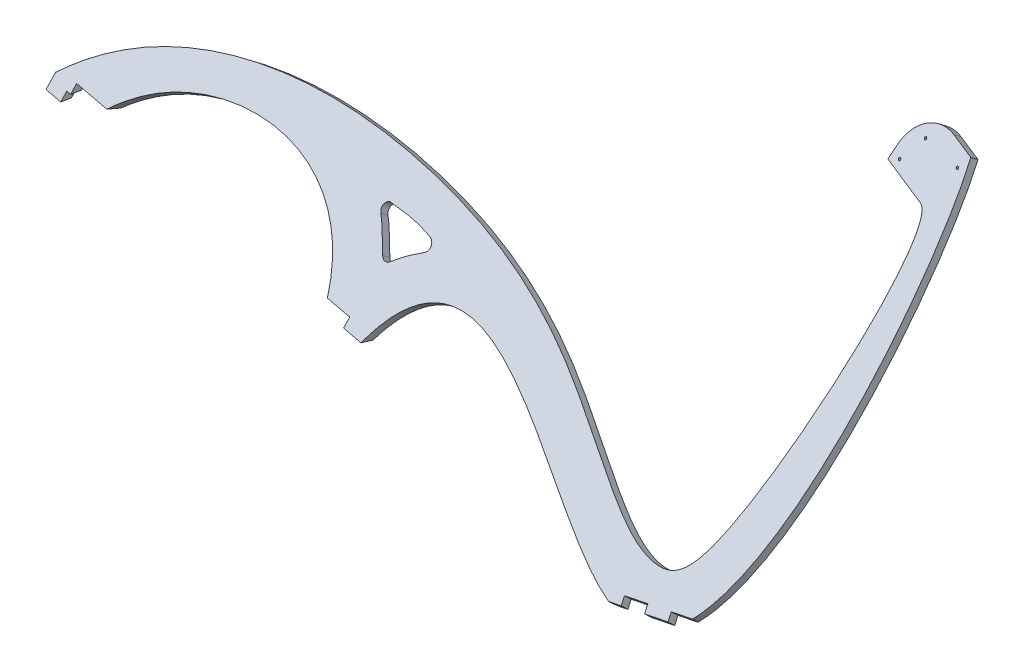
SolidWorks part; units mm, degrees
ref_plane "Front Plane" through (0, 0, 0) normal (0, 0, 1) x (1, 0, 0)
ref_plane "Top Plane" through (0, 0, 0) normal (0, 1, 0) x (1, 0, 0)
ref_plane "Right Plane" through (0, 0, 0) normal (1, 0, 0) x (0, 0, -1)
ref_plane "Plane1" through (247.5119, 247.5119, -680.0333) normal (-0.3236, -0.3236, 0.8891) x (0.9462, -0.1107, 0.3041)
ref_axis "Axis1" through (1039.3698, 513.9591, -294.8417) along (-0.9454, 0.1498, -0.2896)
sketch "Sketch1" plane through (17.4996, -61.6138, -87.0647) normal (0.1568, -0.5697, -0.8068) x (-0.9876, -0.0871, -0.1305)
  line L0 (-848.888, 45.7598) -> (366.2309, 175.3119) construction
  line L1 (334.7635, 186.6404) -> (364.595, 189.8209) construction
  line L2 (-225.3142, 126.9267) -> (-260.7406, 123.1496)
  line L3 (334.7635, 186.6404) -> (336.3995, 172.1314) construction
  line L4 (365.1946, 183.566) -> (363.5586, 198.075) construction
  line L5 (366.1265, 175.3008) -> (363.5586, 198.075)
  line L6 (-1005.1456, 627.3782) -> (-1005.4224, 627.1712) construction
  line L7 (366.1265, 175.3008) -> (336.3995, 172.1314)
  line L8 (336.3995, 172.1314) -> (334.7635, 186.6404)
  line L9 (-1058.1671, 586.5088) -> (-906.3804, 631.7276) construction
  line L10 (-1032.2646, 594.2254) -> (-731.2, 683.9156) construction
  line L11 (-1026.3239, 684.8448) -> (-924.6621, 715.1309)
  line L12 (-924.6621, 715.1309) -> (-906.3804, 631.7276)
  line L13 (-927.8383, 59.6968) -> (-770.1655, 32.5073) construction
  line L14 (-711.049, 22.3131) -> (-907.4588, 56.1825) construction
  line L15 (334.7635, 186.6404) -> (326.9877, 185.8113)
  line L16 (-927.8383, 59.6968) -> (-923.59, 84.3331) construction
  line L17 (-923.59, 84.3331) -> (-765.9171, 57.1436) construction
  line L18 (-227.329, 141.3953) -> (-225.3142, 126.9267)
  line L19 (-765.9171, 57.1436) -> (-770.1655, 32.5073) construction
  line L20 (-849.0019, 46.102) -> (-841.4008, 90.1812) construction
  line L21 (-982.2737, 609.1182) -> (-906.3804, 631.7276)
  line L22 (-260.7406, 123.1496) -> (-225.3142, 126.9267) construction
  line L23 (-227.329, 141.3953) -> (-225.3142, 126.9267) construction
  line L24 (325.4398, 200.3297) -> (264.5058, 193.8331)
  line L25 (-227.329, 141.3953) -> (-182.2193, 146.2047)
  line L26 (-849.0019, 46.102) -> (-854.1752, 16.102) construction
  line L27 (-182.2193, 146.2047) -> (-227.329, 141.3953)
  line L28 (-227.329, 141.3953) -> (-257.1753, 138.2132)
  line L29 (-227.329, 141.3953) -> (-257.1753, 138.2132) construction
  line L30 (-182.2193, 146.2047) -> (-227.329, 141.3953) construction
  line L31 (325.4398, 200.3297) -> (264.5058, 193.8331) construction
  line L32 (325.4398, 200.3297) -> (326.9877, 185.8113)
  line L33 (325.4398, 200.3297) -> (326.9877, 185.8113)
  line L34 (325.4398, 200.3297) -> (264.5058, 193.8331)
  ellipse E0 centre (76.7309, -163.7713) end of major axis (10.5208, 457.2386) minor radius 355.7705 (-257.1753, 138.2132) -> (-260.7406, 123.1496) ccw construction
  spline S0 degree 3 poles (-982.2737, 609.1182) (-1029.6096, 598.293) (-938.6177, 119.1677) (-844.1848, 81.5427) (-750.4586, 111.4734) (-542.5515, 265.8857) (-159.6817, 379.449) (217.4268, 343.7924) (363.5586, 198.075) knots 0 0 0 0 0.220807 0.303233 0.390142 0.497709 0.653994 1 1 1 1
  spline S1 degree 3 poles (-182.2193, 146.2047) (-137.5596, 288.6615) (94.0163, 311.7011) (234.6001, 223.2366) (264.5058, 193.8331) knots 0 0 0 0 0.72161 0.964477 0.964477 0.964477 0.964477
  spline S2 degree 3 poles (-1026.3239, 684.8448) (-1056.5086, 520.532) (-1000.6634, -421.934) (-393.994, 393.2132) (-260.7406, 123.1496) knots 0 0 0 0 0.513113 1 1 1 1
  dimension "D2" = 80
  dimension "D3" = 80
  dimension "D4" = 25
  dimension "D5" = 30
ref_plane "Plane2" through (32.3075, 32.3075, -88.7641) normal (-0.3236, -0.3236, 0.8891) x (0.9462, -0.1107, 0.3041)
ref_plane "Plane3" through (734.8882, 76.1719, 295.2017) normal (-0.9237, -0.0957, -0.371) x (-0.3691, -0.0383, 0.9286)
ref_axis "Axis2" through (710.5526, 368.3269, 280.3979) along (0.2052, -0.9413, -0.2679)
sketch "Sketch2" plane through (11.2801, -57.0409, 57.2996) normal (0.1382, -0.6987, 0.7019) x (0.9904, 0.0904, -0.105)
  line L12 (847.9784, 66.4873) -> (852.7457, 41.946) construction
  line L18 (774.2138, 26.6907) -> (931.2777, 57.2013) construction
  line L19 (931.2777, 57.2013) -> (926.5104, 81.7426) construction
  line L20 (926.5104, 81.7426) -> (769.4465, 51.2319) construction
  line L21 (769.4465, 51.2319) -> (774.2138, 26.6907) construction
  line L22 (852.7457, 41.946) -> (858.4665, 12.4965) construction
  dimension "D1" = 25
  dimension "D2" = 30
ref_plane "Plane4" through (744.3294, 384.7233, 304.283) normal (-0.3236, 0.8891, 0.3236) x (0.9397, 0.342, 0)
sketch "Sketch4" plane through (744.3294, 384.7233, 304.283) normal (-0.3236, 0.8891, 0.3236) x (0.9397, 0.342, 0)
  line L0 (75.8923, -10) -> (123.4751, -10)
  line L1 (123.4751, -10) -> (123.4751, 153.8205)
  line L2 (75.8923, 48.8458) -> (75.8923, 153.8205) construction
  line L3 (75.8923, 153.8205) -> (-79.8307, 153.8205)
  line L4 (-79.8307, -10) -> (-79.8307, 153.8205)
  line L5 (123.4751, 153.8205) -> (75.8923, 153.8205)
  line L6 (75.8923, 48.8458) -> (75.8923, -10) construction
  line L7 (75.8923, -10) -> (-79.8307, -10)
  line L8 (80, -10) -> (-43.6414, -10) construction
  dimension "D1" = 155.723
  dimension "D2" = 163.8205
  dimension "D3" = 58.8458
  dimension "D4" = 47.5828
extrude "Boss-Extrude2" add sketch "Sketch1" along normal blind 12 separate body contours L11 S2 L2 S1 S0 L21 L12 region at (486.3942, 197.6823, -179.0082)
fillet "Fillet1" radius 60 1 edges at (934.526, 599.9752, -383.3936)
fillet "Fillet2" radius 30 1 edges at (990.9986, 518.3564, -314.786)
sketch "Sketch13" plane through (18.832, -68.408, -96.8824) normal (0.1568, -0.5697, -0.8068) x (-0.9876, -0.0906, -0.128)
  arc A0 (-235.8752, 221.376) -> (-250.639, 219.3586) centre (-244.1602, 226.976) cw
  arc A1 (-295.3968, 250.3387) -> (-293.0699, 268.7568) centre (-290.5424, 259.0814) cw
  arc A2 (-213.0974, 278.6163) -> (-205.5275, 261.6168) centre (-212.6601, 268.6259) cw
  spline S0 degree 3 poles (-293.0699, 268.7568) (-292.4947, 268.907) (-261.9123, 276.8067) (-239.7929, 277.4476) (-213.0974, 278.6163) knots 0.445827 0.445827 0.445827 0.445827 0.44834 0.580052 0.580052 0.580052 0.580052
  spline S3 degree 3 poles (-295.3968, 250.3387) (-282.0863, 242.9481) (-266.8858, 232.7869) (-252.8897, 221.2729) (-250.639, 219.3586) knots 0.719716 0.719716 0.719716 0.719716 0.79687 0.811921 0.811921 0.811921 0.811921
  spline S5 degree 3 poles (-235.8752, 221.376) (-232.7991, 225.9271) (-220.1586, 243.2214) (-212.8497, 254.1656) (-205.5275, 261.6168) knots 0.147762 0.147762 0.147762 0.147762 0.170979 0.239181 0.239181 0.239181 0.239181
  dimension "D1" = 10
sketch "Sketch14" plane through (10.9247, -56.0037, 56.203) normal (0.1364, -0.6993, 0.7017) x (0.9907, 0.096, -0.0969)
  line L0 (816.7452, 27.0278) -> (821.0315, 3.7163)
  line L1 (821.0315, 3.7163) -> (860.3924, 10.8394)
  line L2 (860.3924, 10.8394) -> (856.0857, 34.2614)
  line L3 (895.4262, 41.495) -> (899.7532, 17.9626)
  line L4 (899.7532, 17.9626) -> (940.8385, 25.3978)
  line L5 (940.8385, 25.3978) -> (940.8385, 74.0524)
  line L7 (895.4262, 41.495) -> (856.0857, 34.2614)
  line L10 (816.7452, 27.0278) -> (792.6014, 22.5885)
  line L23 (827.9034, 545.3306) -> (696.2019, 529.5358)
  line L24 (688.0254, 516.1063) -> (698.6127, 487.7765)
  line L29 (698.6127, 487.7765) -> (780.079, 496.7776)
  line L30 (-323.9964, 221.96) -> (-316.4535, 220.9381)
  line L31 (-323.9964, 221.96) -> (-316.4535, 220.9381)
  line L36 (-316.4535, 220.9381) -> (-314.2, 237.5723)
  line L38 (268.023, 141.7575) -> (270.8794, 153.8295)
  line L39 (796.2366, 21.4509) -> (817.0727, 25.2821)
  line L40 (817.0727, 25.2821) -> (818.8085, 15.8459)
  line L41 (820.9388, 15.46) -> (858.2628, 22.4606)
  line L42 (858.2628, 22.4606) -> (856.4132, 32.5157)
  line L43 (856.4132, 32.5157) -> (895.7537, 39.7493)
  line L44 (895.7537, 39.7493) -> (897.5775, 29.8346)
  line L45 (897.5775, 29.8346) -> (908.6107, 31.904)
  line L46 (827.9034, 545.3306) -> (696.2019, 529.5358)
  line L47 (688.0254, 516.1063) -> (698.6127, 487.7765)
  line L52 (698.6127, 487.7765) -> (780.079, 496.7776)
  line L59 (-316.4535, 220.9381) -> (-314.2, 237.5723)
  line L61 (268.023, 141.7575) -> (270.8794, 153.8295)
  line L68 (895.4262, 41.495) -> (856.0857, 34.2614) construction
  line L111 (774.7231, 19.3012) -> (931.2974, 48.0907)
  line L112 (774.7231, 19.3012) -> (931.2974, 48.0907) construction
  line L133 (-354.4963, 221.3356) -> (-356.1399, 209.4041)
  line L134 (-354.4963, 221.3356) -> (-356.1399, 209.4041)
  line L135 (-326.2139, 205.5917) -> (-323.9964, 221.96)
  line L136 (-326.2139, 205.5917) -> (-323.9964, 221.96)
  line L161 (229.6776, 146.9522) -> (268.023, 141.7575)
  line L162 (229.6776, 146.9522) -> (268.023, 141.7575)
  line L163 (-356.1399, 209.4041) -> (-326.2139, 205.5917)
  line L164 (-356.1399, 209.4041) -> (-326.2139, 205.5917)
  line L213 (231.9311, 163.5864) -> (229.6776, 146.9522)
  line L214 (231.9311, 163.5864) -> (229.6776, 146.9522)
  line L307 (839.016, 527.501) -> (827.9034, 545.3306)
  line L308 (839.016, 527.501) -> (827.9034, 545.3306)
  line L1386 (-314.2, 237.5723) -> (-257.8212, 229.9345)
  line L1387 (-314.2, 237.5723) -> (-257.8212, 229.9345)
  line L1388 (181.1707, 170.4631) -> (231.9311, 163.5864)
  line L1389 (181.1707, 170.4631) -> (231.9311, 163.5864)
  arc A3 (818.8085, 15.8459) -> (820.9388, 15.46) centre (851.6332, 190.9851) ccw
  arc A6 (696.2019, 529.5358) -> (688.0254, 516.1063) centre (697.3927, 519.607) ccw
  arc A7 (696.2019, 529.5358) -> (688.0254, 516.1063) centre (697.3927, 519.607) ccw
  arc A8 (808.4728, 483.3916) -> (780.079, 496.7776) centre (783.3736, 466.959) ccw
  arc A9 (808.4728, 483.3916) -> (780.079, 496.7776) centre (783.3736, 466.959) ccw
  spline S4 degree 3 poles (-1756.6972, -623.169) (184.1664, 1394.5192) (924.7649, 665.4068) (891.9303, 117.5432) (838.2684, 60.3124) (474.8556, 278.5473) (312.4277, 323.5108) (174.3715, 354.2007) (-442.5977, 436.0656) (-467.0672, -131.6514) (1749.2149, 2354.597) knots -0.550705 -0.550705 -0.550705 -0.550705 0.151162 0.162646 0.216715 0.325184 0.582296 0.642884 0.931064 1.246753 1.246753 1.246753 1.246753 only from (808.4728, 483.3916) to (-354.4963, 221.3356)
  spline S5 degree 3 poles (808.4728, 483.3916) (871.14, 387.6736) (900.8711, 266.7257) (891.9303, 117.5432) (838.2684, 60.3124) (474.8556, 278.5473) (312.4277, 323.5108) (174.3715, 354.2007) (-202.0112, 404.1424) (-347.3444, 237.3169) (-354.4963, 221.3356) knots 0.007748 0.007748 0.007748 0.007748 0.151162 0.162646 0.216715 0.325184 0.582296 0.642884 0.931064 0.987649 0.987649 0.987649 0.987649
  spline S6 degree 3 poles (803.3764, -2777.8083) (-169.5613, 382.713) (675.2368, 264.3028) (1210.9342, -407.2256) (982.0087, 2981.9127) knots -0.591806 -0.591806 -0.591806 -0.591806 0.313933 1.227742 1.227742 1.227742 1.227742 only from (270.8794, 153.8295) to (796.2366, 21.4509)
  spline S7 degree 3 poles (3202.4259, 1795.1061) (-293.1759, 310.4376) (935.7826, -225.0911) (947.8695, 114.2472) (948.4185, 177.4278) (943.8345, 462.0378) (493.9857, 1096.7584) (2061.0907, -2211.1658) knots -0.155184 -0.155184 -0.155184 -0.155184 0.721644 0.729568 0.737326 0.884726 1.333425 1.333425 1.333425 1.333425 only from (908.6107, 31.904) to (839.016, 527.501)
  spline S8 degree 3 poles (2565.5213, -728.5577) (-573.6663, -6.8548) (-287.7274, 249.4306) (199.9126, 408.1873) (773.9931, -319.828) (-2601.9944, -793.6131) knots -0.716657 -0.716657 -0.716657 -0.716657 0.127272 0.42315 2.234576 2.234576 2.234576 2.234576 only from (-257.8212, 229.9345) to (181.1707, 170.4631)
  spline S9 degree 3 poles (-257.8212, 229.9345) (-243.1127, 243.9824) (-165.2805, 289.2946) (-13.244, 338.7918) (155.7697, 256.2057) (181.1707, 170.4631) knots 0.024401 0.024401 0.024401 0.024401 0.127272 0.42315 0.944537 0.944537 0.944537 0.944537
  spline S10 degree 3 poles (270.8794, 153.8295) (347.2792, 247.1748) (551.3718, 165.3716) (732.221, 41.9755) (792.6014, 22.5885) knots 0 0 0 0 0.313933 0.498958 0.498958 0.498958 0.498958
  spline S11 degree 3 poles (940.8385, 74.0524) (944.3601, 83.4114) (947.2378, 96.5123) (947.8695, 114.2472) (948.4185, 177.4278) (946.3656, 304.8877) (857.9002, 497.3845) (839.016, 527.501) knots 0.690681 0.690681 0.690681 0.690681 0.721644 0.729568 0.737326 0.884726 1 1 1 1
  dimension "D2" = 40
  dimension "D1" = 0
extrude "Cut-Extrude1" cut sketch "Sketch14" along normal blind 40
sketch "Sketch15" plane through (12.5616, -64.3947, 64.6238) normal (0.1364, -0.6993, 0.7017) x (0.9907, 0.0964, -0.0965)
  line L1 (731.997, 0) -> (975.3461, 0)
  line L2 (731.997, 0) -> (731.997, 73.2)
  line L3 (731.997, 73.2) -> (975.3461, 73.2)
  line L4 (975.3461, 0) -> (975.3461, 73.2)
extrude "Cut-Extrude2" cut sketch "Sketch15" along normal blind 30
extrude "Cut-Extrude3" cut sketch "Sketch13" against normal blind 30
sketch "Sketch16" plane through (0, 73.7489, 0) normal (0, 1, 0) x (1, 0, 0)
  line L24 (260.0825, -154.1644) -> (242.3962, -157.6022)
  line L25 (242.3962, -157.6022) -> (239.1932, -141.1245)
  line L26 (239.1932, -141.1245) -> (268.6421, -135.4002)
  line L27 (273.5034, -90.8566) -> (263.5353, -88.0514)
  line L28 (263.0272, 95.2328) -> (273.2396, 98.1679)
  line L29 (272.0458, 133.1647) -> (242.5818, 138.8919)
  line L30 (242.5818, 138.8919) -> (245.6303, 153.1733)
  line L31 (245.6303, 153.1733) -> (265.1897, 149.3713)
  line L32 (253.7158, 172.4608) -> (164.4554, 252.337)
  line L33 (-262.2531, 271.0115) -> (-291.8318, 276.761)
  line L34 (-297.694, 272.8069) -> (-306.2804, 228.6337)
  line L35 (-321.0693, 211.2943) -> (-358.5166, 191.5354)
  line L36 (-374.5434, 166.3252) -> (-362.4024, 172.7314)
  line L37 (-362.4024, 172.7314) -> (-356.8024, 162.1182)
  line L38 (-356.8024, 162.1182) -> (-383.3354, 148.1182)
  line L39 (-385.1916, 115.9646) -> (-384.719, 115.8005)
  line L40 (-384.719, -110.4058) -> (-385.1916, -110.5699)
  line L41 (-383.3354, -142.7234) -> (-356.8024, -156.7234)
  line L42 (-356.8024, -156.7234) -> (-362.4024, -167.3366)
  line L43 (-374.5434, 166.3252) -> (-362.4024, 172.7314)
  line L44 (-358.5166, -186.1407) -> (-321.0693, -205.8996)
  line L45 (-306.2804, -223.2389) -> (-297.694, -267.4121)
  line L46 (-291.8318, -271.3662) -> (-262.2531, -265.6167)
  line L47 (167.0832, -244.5656) -> (253.618, -165.4645)
  line L48 (260.0825, -154.1644) -> (242.3962, -157.6022)
  line L49 (242.3962, -157.6022) -> (239.1932, -141.1245)
  line L50 (239.1932, -141.1245) -> (268.6421, -135.4002)
  line L51 (273.5034, -90.8566) -> (263.5353, -88.0514)
  line L54 (242.5818, 138.8919) -> (245.6303, 153.1733)
  line L55 (245.6303, 153.1733) -> (265.1897, 149.3713)
  line L56 (253.7158, 172.4608) -> (164.4554, 252.337)
  line L57 (-262.2531, 271.0115) -> (-291.8318, 276.761)
  line L58 (-297.694, 272.8069) -> (-306.2804, 228.6337)
  line L59 (-321.0693, 211.2943) -> (-358.5166, 191.5354)
  line L60 (-362.4024, -167.3366) -> (-374.5434, -160.9305)
  line L61 (-362.4024, 172.7314) -> (-356.8024, 162.1182)
  line L62 (-356.8024, 162.1182) -> (-383.3354, 148.1182)
  line L63 (-385.1916, 115.9646) -> (-384.719, 115.8005)
  line L64 (-384.719, -110.4058) -> (-385.1916, -110.5699)
  line L65 (-383.3354, -142.7234) -> (-356.8024, -156.7234)
  line L66 (-356.8024, -156.7234) -> (-362.4024, -167.3366)
  line L67 (-362.4024, -167.3366) -> (-374.5434, -160.9305)
  line L68 (-358.5166, -186.1407) -> (-321.0693, -205.8996)
  line L69 (-306.2804, -223.2389) -> (-297.694, -267.4121)
  line L70 (-291.8318, -271.3662) -> (-262.2531, -265.6167)
  line L71 (167.0832, -244.5656) -> (253.618, -165.4645)
  line L172 (242.5818, 138.8919) -> (234.4121, 100.6192)
  line L173 (234.4121, 100.6192) -> (263.0272, 95.2328)
  arc A27 (268.6421, -135.4002) -> (280.3406, -103.4614) centre (-58.9389, 2.6974) ccw
  arc A28 (280.3406, -103.4614) -> (273.5034, -90.8566) centre (270.7945, -100.4827) ccw
  arc A29 (263.5353, -88.0514) -> (263.0272, 95.2328) centre (-58.9389, 2.6974) ccw
  arc A30 (273.2396, 98.1679) -> (280.0044, 110.8179) centre (270.4774, 107.7788) ccw
  arc A31 (280.0044, 110.8179) -> (272.0458, 133.1647) centre (-58.9389, 2.6974) ccw
  arc A32 (265.1897, 149.3713) -> (253.7158, 172.4608) centre (-58.9389, 2.6974) ccw
  arc A33 (164.4554, 252.337) -> (-258.3232, 271.9016) centre (-58.9389, 2.6974) ccw
  arc A34 (-262.2531, 271.0115) -> (-258.3232, 271.9016) centre (-261.299, 275.9196) ccw
  arc A35 (-291.8318, 276.761) -> (-297.694, 272.8069) centre (-292.7858, 271.8528) ccw
  arc A36 (-306.2804, 228.6337) -> (-321.0693, 211.2943) centre (-58.9389, 2.6974) ccw
  arc A37 (-358.5166, 191.5354) -> (-362.3857, 187.9007) centre (-353.85, 182.6911) ccw
  arc A38 (-362.3857, 187.9007) -> (-374.5434, 166.3252) centre (-58.9389, 2.6974) ccw
  arc A39 (-383.3354, 148.1182) -> (-391.2598, 128.9633) centre (-58.9389, 2.6974) ccw
  arc A40 (-391.2598, 128.9633) -> (-385.1916, 115.9646) centre (-381.9118, 125.4115) ccw
  arc A41 (-378.4608, 103.3491) -> (-384.719, 115.8005) centre (-387.9988, 106.3537) ccw
  arc A42 (-378.4608, 103.3491) -> (-378.4608, -97.9544) centre (-58.9389, 2.6974) ccw
  arc A43 (-384.719, -110.4058) -> (-378.4608, -97.9544) centre (-387.9988, -100.9589) ccw
  arc A44 (-385.1916, -110.5699) -> (-391.2598, -123.5685) centre (-381.9118, -120.0167) ccw
  arc A45 (-391.2598, -123.5685) -> (-383.3354, -142.7234) centre (-58.9389, 2.6974) ccw
  arc A46 (-374.5434, -160.9305) -> (-362.3857, -182.506) centre (-58.9389, 2.6974) ccw
  arc A47 (-362.3857, -182.506) -> (-358.5166, -186.1407) centre (-353.85, -177.2963) ccw
  arc A48 (-321.0693, -205.8996) -> (-306.2804, -223.2389) centre (-58.9389, 2.6974) ccw
  arc A49 (-297.694, -267.4121) -> (-291.8318, -271.3662) centre (-292.7858, -266.4581) ccw
  arc A50 (-258.3232, -266.5069) -> (-262.2531, -265.6167) centre (-261.299, -270.5249) ccw
  arc A51 (-258.3232, -266.5069) -> (167.0832, -244.5656) centre (-58.9389, 2.6974) ccw
  arc A52 (253.618, -165.4645) -> (255.7223, -162.7371) centre (246.871, -158.0836) ccw
  arc A53 (255.7223, -162.7371) -> (260.0825, -154.1644) centre (-58.9389, 2.6974) ccw
  arc A54 (268.6421, -135.4002) -> (280.3406, -103.4614) centre (-58.9389, 2.6974) ccw
  arc A55 (280.3406, -103.4614) -> (273.5034, -90.8566) centre (270.7945, -100.4827) ccw
  arc A56 (263.5353, -88.0514) -> (263.0272, 95.2328) centre (-58.9389, 2.6974) ccw
  arc A59 (265.1897, 149.3713) -> (253.7158, 172.4608) centre (-58.9389, 2.6974) ccw
  arc A60 (164.4554, 252.337) -> (-258.3232, 271.9016) centre (-58.9389, 2.6974) ccw
  arc A61 (-262.2531, 271.0115) -> (-258.3232, 271.9016) centre (-261.299, 275.9196) ccw
  arc A62 (-291.8318, 276.761) -> (-297.694, 272.8069) centre (-292.7858, 271.8528) ccw
  arc A63 (-306.2804, 228.6337) -> (-321.0693, 211.2943) centre (-58.9389, 2.6974) ccw
  arc A64 (-358.5166, 191.5354) -> (-362.3857, 187.9007) centre (-353.85, 182.6911) ccw
  arc A65 (-362.3857, 187.9007) -> (-374.5434, 166.3252) centre (-58.9389, 2.6974) ccw
  arc A66 (-383.3354, 148.1182) -> (-391.2598, 128.9633) centre (-58.9389, 2.6974) ccw
  arc A67 (-391.2598, 128.9633) -> (-385.1916, 115.9646) centre (-381.9118, 125.4115) ccw
  arc A68 (-378.4608, 103.3491) -> (-384.719, 115.8005) centre (-387.9988, 106.3537) ccw
  arc A69 (-378.4608, 103.3491) -> (-378.4608, -97.9544) centre (-58.9389, 2.6974) ccw
  arc A70 (-384.719, -110.4058) -> (-378.4608, -97.9544) centre (-387.9988, -100.9589) ccw
  arc A71 (-385.1916, -110.5699) -> (-391.2598, -123.5685) centre (-381.9118, -120.0167) ccw
  arc A72 (-391.2598, -123.5685) -> (-383.3354, -142.7234) centre (-58.9389, 2.6974) ccw
  arc A73 (-374.5434, -160.9305) -> (-362.3857, -182.506) centre (-58.9389, 2.6974) ccw
  arc A74 (-362.3857, -182.506) -> (-358.5166, -186.1407) centre (-353.85, -177.2963) ccw
  arc A75 (-321.0693, -205.8996) -> (-306.2804, -223.2389) centre (-58.9389, 2.6974) ccw
  arc A76 (-297.694, -267.4121) -> (-291.8318, -271.3662) centre (-292.7858, -266.4581) ccw
  arc A77 (-258.3232, -266.5069) -> (-262.2531, -265.6167) centre (-261.299, -270.5249) ccw
  arc A78 (-258.3232, -266.5069) -> (167.0832, -244.5656) centre (-58.9389, 2.6974) ccw
  arc A79 (253.618, -165.4645) -> (255.7223, -162.7371) centre (246.871, -158.0836) ccw
  arc A80 (255.7223, -162.7371) -> (260.0825, -154.1644) centre (-58.9389, 2.6974) ccw
  dimension "D1" = 0
extrude "Cut-Extrude6" cut sketch "Sketch16" against normal blind 80
sketch "Sketch17" plane through (0, 61.7489, 0) normal (0, 1, 0) x (1, 0, 0)
  line L0 (-311.5127, -236.2134) -> (-318.0238, -202.7164)
  line L1 (-318.0238, -202.7164) -> (-348.4097, -206.5409)
  line L2 (-312.3696, 238.2904) -> (-319.0246, 205.8984)
  line L3 (-319.0246, 205.8984) -> (-348.4097, 211.9357)
  line L9 (-338.8804, 258.3175) -> (-309.5341, 252.6132)
  line L10 (-309.5341, 252.6132) -> (-312.3696, 238.2904)
  line L11 (-312.3696, 238.2904) -> (-341.8189, 244.0148)
  line L12 (-341.8189, 244.0148) -> (-348.4097, 211.9357)
  line L13 (-348.4097, -206.5409) -> (-341.1305, -241.9706)
  line L14 (-341.1305, -241.9706) -> (-311.5127, -236.2134)
  line L15 (-311.5127, -236.2134) -> (-308.3097, -252.6912)
  line L16 (-308.3097, -252.6912) -> (-337.7522, -258.4142)
  line L17 (-336.5016, 269.8957) -> (-338.8804, 258.3175)
  line L18 (-338.8804, 258.3175) -> (-309.5341, 252.6132)
  line L19 (-309.5341, 252.6132) -> (-312.3696, 238.2904)
  line L20 (-312.3696, 238.2904) -> (-341.8189, 244.0148) construction
  line L21 (-341.8189, 244.0148) -> (-348.4097, 211.9357) construction
  line L22 (-348.4097, -206.5409) -> (-341.1305, -241.9706) construction
  line L23 (-341.1305, -241.9706) -> (-311.5127, -236.2134) construction
  line L24 (-311.5127, -236.2134) -> (-308.3097, -252.6912)
  line L25 (-308.3097, -252.6912) -> (-337.7522, -258.4142)
  line L26 (-336.5016, 269.8957) -> (-338.8804, 258.3175)
  line L46 (-337.7522, -258.4142) -> (-336.0706, -266.5988)
  line L47 (-337.7522, -258.4142) -> (-336.0706, -266.5988)
  line L48 (-306.5509, -286.0561) -> (-285.9822, -281.8302)
  line L49 (-306.5509, -286.0561) -> (-285.9822, -281.8302)
  line L50 (-288.3339, 285.5217) -> (-306.9819, 289.353)
  line L51 (-288.3339, 285.5217) -> (-306.9819, 289.353)
  line L52 (280.7997, 107.3775) -> (325.4285, 113.4656)
  line L53 (325.4285, 113.4656) -> (303.1141, 175.1338)
  line L54 (303.1141, 175.1338) -> (253.959, 171.4432)
  arc A10 (-351.5391, 204.6018) -> (-348.4097, 211.9357) centre (-368.0005, 215.9607) ccw
  arc A11 (-351.5391, 204.6018) -> (-351.5391, -199.207) centre (-58.9389, 2.6974) ccw
  arc A12 (-348.4097, -206.5409) -> (-351.5391, -199.207) centre (-368.0005, -210.5659) ccw
  arc A13 (-336.0706, -266.5988) -> (-306.5509, -286.0561) centre (-311.5821, -261.5676) ccw
  arc A14 (-336.0706, -266.5988) -> (-306.5509, -286.0561) centre (-311.5821, -261.5676) ccw
  arc A15 (-266.3641, -286.0154) -> (-285.9822, -281.8302) centre (-280.9509, -306.3187) ccw
  arc A16 (-266.3641, -286.0154) -> (-268.5613, 289.8188) centre (-58.9389, 2.6974) ccw
  arc A17 (-266.3641, -286.0154) -> (-285.9822, -281.8302) centre (-280.9509, -306.3187) ccw
  arc A18 (-288.3339, 285.5217) -> (-268.5613, 289.8188) centre (-283.3027, 310.0102) ccw
  arc A19 (-288.3339, 285.5217) -> (-268.5613, 289.8188) centre (-283.3027, 310.0102) ccw
  arc A20 (-351.5391, 204.6018) -> (-348.4097, 211.9357) centre (-368.0005, 215.9607) ccw
  arc A21 (-351.5391, 204.6018) -> (-351.5391, -199.207) centre (-58.9389, 2.6974) ccw
  arc A22 (-348.4097, -206.5409) -> (-351.5391, -199.207) centre (-368.0005, -210.5659) ccw
  arc A23 (-306.9819, 289.353) -> (-336.5016, 269.8957) centre (-312.0131, 264.8645) ccw
  arc A24 (-306.9819, 289.353) -> (-336.5016, 269.8957) centre (-312.0131, 264.8645) ccw
  arc A26 (-266.3641, -286.0154) -> (280.7997, 107.3775) centre (-58.9389, 2.6974) ccw
  arc A32 (253.959, 171.4432) -> (-268.5613, 289.8188) centre (-58.9389, 2.6974) ccw
  dimension "D1" = 0
extrude "Cut-Extrude7" cut sketch "Sketch17" against normal blind 20
sketch "Sketch18" plane through (0, 49.7489, 0) normal (0, -1, 0) x (1, 0, 0)
  line L1 (-360.3193, -259.7562) -> (-287.016, -259.7562)
  line L2 (-360.3193, -259.7562) -> (-360.3193, -202.9049)
  line L3 (-360.3193, -202.9049) -> (-287.016, -202.9049)
  line L4 (-287.016, -259.7562) -> (-287.016, -202.9049)
extrude "Cut-Extrude8" cut sketch "Sketch18" along normal blind 20
sketch "Sketch20" plane through (18.832, -68.408, -96.8824) normal (0.1568, -0.5697, -0.8068) x (-0.9876, -0.0904, -0.1281)
  circle A0 centre (-1025.6141, 605.4035) radius 2 construction
  circle A1 centre (-1016.9498, 662.1762) radius 2
  circle A2 centre (-950.9144, 671.511) radius 2
  circle A3 centre (-926.7964, 635.0878) radius 2
  dimension "D7" = 4
  dimension "D1" = 57.4301
  dimension "D2" = 18.4182
  dimension "D3" = 12.6795
  dimension "D4" = 66.6919
  dimension "D5" = 43.6844
  dimension "D6" = 103.18
extrude "Cut-Extrude9" cut sketch "Sketch20" against normal blind 30
